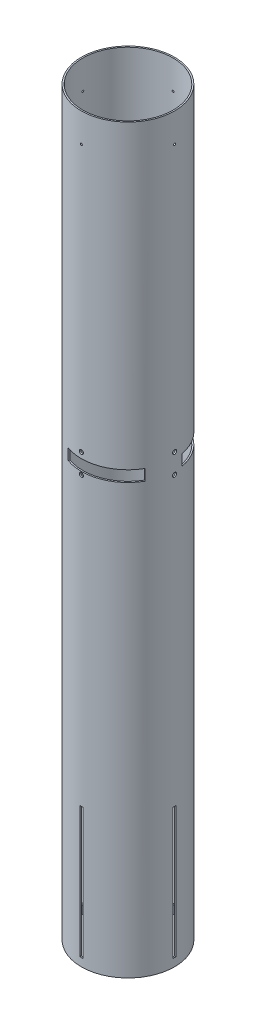
SolidWorks part; units mm, degrees
material "A-Glass Fiber"
ref_plane "Front Plane" through (0, 0, 0) normal (0, 0, 1) x (1, 0, 0)
ref_plane "Top Plane" through (0, 0, 0) normal (0, 1, 0) x (1, 0, 0)
ref_plane "Right Plane" through (0, 0, 0) normal (1, 0, 0) x (0, 0, -1)
sketch "Sketch1" plane through (0, 0, 0) normal (0, 1, 0) x (1, 0, 0)
  circle A0 centre (0, 0) radius 49.53
  circle A1 centre (0, 0) radius 51.1048
  dimension "D1" = 99.06
  dimension "D2" = 102.2096
extrude "Boss-Extrude1" add sketch "Sketch1" along normal blind 812.8
ref_plane "Plane1" through (0, 0, 0) normal (0.7071, 0, 0.7071) x (0.7071, 0, -0.7071)
ref_axis "Axis1" through (0, 812.8, 0) along (0, -1, 0)
sketch "Sketch2" plane through (0, 0, 0) normal (1, 0, 0) x (0, 0, -1)
  line L0 (0, 0) -> (0, 8.89)
  line L1 (1.5875, 8.89) -> (-1.5875, 8.89)
  line L2 (1.5875, 8.89) -> (1.5875, 152.4)
  line L3 (1.5875, 152.4) -> (-1.5875, 152.4)
  line L4 (-1.5875, 8.89) -> (-1.5875, 152.4)
  line L5 (1.5875, 8.89) -> (-1.5875, 152.4) construction
  line L6 (1.5875, 152.4) -> (-1.5875, 8.89) construction
  line L7 (51.1048, 812.8) -> (-51.1048, 812.8) construction
  line L8 (51.1048, 812.8) -> (-51.1048, 812.8)
  line L9 (0, 812.8) -> (0, 488.95)
  line L10 (-51.1048, 0) -> (51.1048, 0) construction
  circle A0 centre (0, 488.95) radius 2.25
  point P0 (0, 80.645)
  dimension "D4" = 4.5
  dimension "D1" = 3.175
  dimension "D5" = 488.95
  dimension "D3" = 152.4
  dimension "D2" = 8.89
extrude "Cut-Extrude1" cut sketch "Sketch2" against normal through all contours L4 L1 L2 L3 region at (0, 80.645, 0)
pattern_circular "CirPattern1" count 4 over 360 about axis through (0, 0, 0) along (0, 1, 0) of "Cut-Extrude1" reverse direction yes
extrude "Cut-Extrude2" cut sketch "Sketch2<3>" against normal through all contours A0 region at (0, 487.404, 1.546)
sketch "Sketch2<3>" plane through (0, 0, 0) normal (1, 0, 0) x (0, 0, -1) same geometry as "Sketch2"
pattern_circular "CirPattern2" count 4 over 360 about axis through (0, 812.8, 0) along (0, -1, 0) of "Cut-Extrude2"
sketch "Sketch3" plane through (0, 0, 0) normal (0.7071, 0, 0.7071) x (0.7071, 0, -0.7071)
  line L0 (0, 0) -> (0, 127) construction
  circle A0 centre (0, 127) radius 3.175
  dimension "D1" = 6.35
  dimension "D2" = 127
extrude "Cut-Extrude3" cut sketch "Sketch3" against normal through all
sketch "Sketch7" plane through (0, 0, 0) normal (0, 1, 0) x (1, 0, 0)
  line L0 (0, 0) -> (-44.2581, -25.5524)
  line L1 (0, 0) -> (0, 93.232) construction
  line L2 (0, 0) -> (-32.8495, 39.1485)
  line L3 (-51.1048, 0) -> (0, 0) construction
  arc A0 (-51.0552, 2.25) -> (-51.0552, -2.25) centre (0, 0) ccw construction
  circle A1 centre (0, 0) radius 49.53 construction
  circle A2 centre (0, 0) radius 51.1048
  circle A3 centre (0, 0) radius 51.1048
  circle A4 centre (0, 0) radius 49.53
  circle A5 centre (0, 0) radius 51.1048 construction
  arc A6 (2.25, 51.0552) -> (-2.25, 51.0552) centre (0, 0) ccw construction
  arc A7 (-51.0552, 2.25) -> (-51.0552, -2.25) centre (0, 0) ccw
  arc A8 (2.25, 51.0552) -> (-2.25, 51.0552) centre (0, 0) ccw
  dimension "D1" = 80
  dimension "D3" = 30
  dimension "D2" = 0
extrude "Cut-Extrude4" cut sketch "Sketch7" against normal blind 12.065 from offset 482.6 contours A4 A3 L0 region at (-43.9137, 0, 24.5741)
pattern_circular "CirPattern3" count 3 over 360 about axis through (0, 812.8, 0) along (0, -1, 0) of "Cut-Extrude4"
pattern_linear "LPattern1" count 2 spacing 21.6916 along (0, -1, 0) of "CirPattern2"
sketch "Sketch8" plane through (0, 0, 0) normal (0, 0, 1) x (1, 0, 0)
  line L0 (49.53, 812.8) -> (-49.53, 812.8) construction
  circle A0 centre (0, 781.05) radius 1.0922
  dimension "D1" = 2.1844
  dimension "D2" = 31.75
extrude "Cut-Extrude5" cut sketch "Sketch8" against normal through all
pattern_circular "CirPattern4" count 4 over 360 about axis through (0, 812.8, 0) along (0, -1, 0) of "Cut-Extrude5"
sketch "Sketch9" plane through (0, 0, 0) normal (0, 0, 1) x (1, 0, 0)
  line L0 (51.1048, 812.8) -> (-51.1048, 812.8) construction
  point P0 (0, 752.856)
  dimension "D1" = 59.944
hole_wizard "1/2 Clearance Hole4" positions "Sketch17" profile "Sketch18" hole size "1/2" standard "ANSI Inch" end condition through all
sketch "Sketch17" plane through (0, 0, 0) normal (0, 0, 1) x (1, 0, 0)
  point P0 (0, 752.856)
sketch "Sketch18" plane through (0, 752.856, 0) normal (1, 0, 0) x (0, -1, 0)
  line L0 (0, 0) -> (0, 51.1048)
  line L1 (0, 51.1048) -> (6.5481, 51.1048)
  line L2 (6.5481, 51.1048) -> (6.5481, 0)
  line L5 (6.5481, 0) -> (0, 0)
  line L11 (0, -6.35) -> (0, 107.95) construction
  dimension "Thru Hole Dia." = 13.0962
  dimension "Thru Hole Depth" = 51.1048
equation "\"D1@Boss-Extrude1\" = \"Aft_Section_Length\""
equation "\"AB_Coupler_OD_Length\"= 1in"
equation "\"AB_Coupling_Section_Length\"= 0.375in"
equation "\"AB_Coupler_Length\"= \"AB_Coupler_OD_Length\" + \"AB_Coupling_Section_Length\" * 2"
equation "\"AB_Coupler_Num_Screws\"= 4"
equation "\"AB_Coupling_Screw_Diameter\"= 4.5mm"
equation "\"Aft_Section_Length\" = 32in"
equation "\"D4@Sketch2\"=\"AB_Coupling_Screw_Diameter\""
equation "\"D1@CirPattern2\"=\"AB_Coupler_Num_Screws\""
equation "\"Rail_Nut_From_Bottom\"= 5in"
equation "\"Rail_Nut_Diam\"= 0.25in"
equation "\"D1@Sketch3\"=\"Rail_Nut_Diam\""
equation "\"D2@Sketch3\"=\"Rail_Nut_From_Bottom\""
equation "\"AB_BKHD_Thickness\"= 0.375in"
equation "\"AB_Mount_From_Bottom\"= 19.25in"
equation "\"Cutout_Angle\" = 60"
equation "\"Motor_OD\" = 54.4mm"
equation "\"Motor_Length\" = 401mm"
equation "\"Mid_Coupler_Length\" = 12in"
equation "\"AB_Paddle_Height\" = 0.375in"
equation "\"Num_Cutouts\" = 4"
equation "\"AB_Coupler_OD\"= 4.024in"
equation "\"AB_Coupler_ID\"= 3.7in"
equation "\"AB_Coupler_Surface_Diameter\"= 3.899in"
equation "\"AB_Central_Bushing_Length\" = 0.75in"
equation "\"Lead_Screw_Dist\" = 2in"
equation "\"Lead_Screw_Diam\" = 0.375in"
equation "\"Lead_Screw_Length\" = \"Mid_Coupler_Length\" + 2*0.375in + 2*0.5in"
equation "\"Paddle_Pin_Offset\" = 0.25in"
equation "\"Paddle_Pin_Radius\" = 2.25*2/3in"
equation "\"Paddle_Gear_OD\" = 3.2in"
equation "\"Fwd_BKHD_From_Top\" = 18in"
equation "\"Body_Tube_OD\"= 4.024in"
equation "\"Body_Tube_ID\"= 3.90in"
equation "\"Coupler_OD\" = 3.899in"
equation "\"Coupler_ID\" = 3.755in"
equation "\"Fwd_Section_Length\" = 20in"
equation "\"Mid_Section_Length\" = 4in"
equation "\"Aft_Upper_Tube_Length\" = 10in"
equation "\"Aft_Lower_Tube_Length\" = 18in"
equation "\"Nosecone_Coupler_Length\" = 5in"
equation "\"Avionics_Bulkhead_Thickness\" = 0.25in"
equation "\"Avionics_Bulkhead_Lip\" = 0.125in"
equation "\"Avionics_Board_Length\" = \"Mid_Coupler_Length\" - 2*\"Avionics_Bulkhead_Lip\""
equation "\"Lead_Screw_Hole_Diam\" = 0.386in"
equation "\"Centering_Ring_Cutout_Dia\"= 1in"
equation "\"D2@Sketch1\"=\"Body_Tube_OD\""
equation "\"D1@Sketch1\"=\"Body_Tube_ID\""
equation "\"D5@Sketch2\"=\"AB_Mount_From_Bottom\""
equation "\"D19@Cut-Extrude4\"=\"AB_Mount_From_Bottom\"-0.25"
